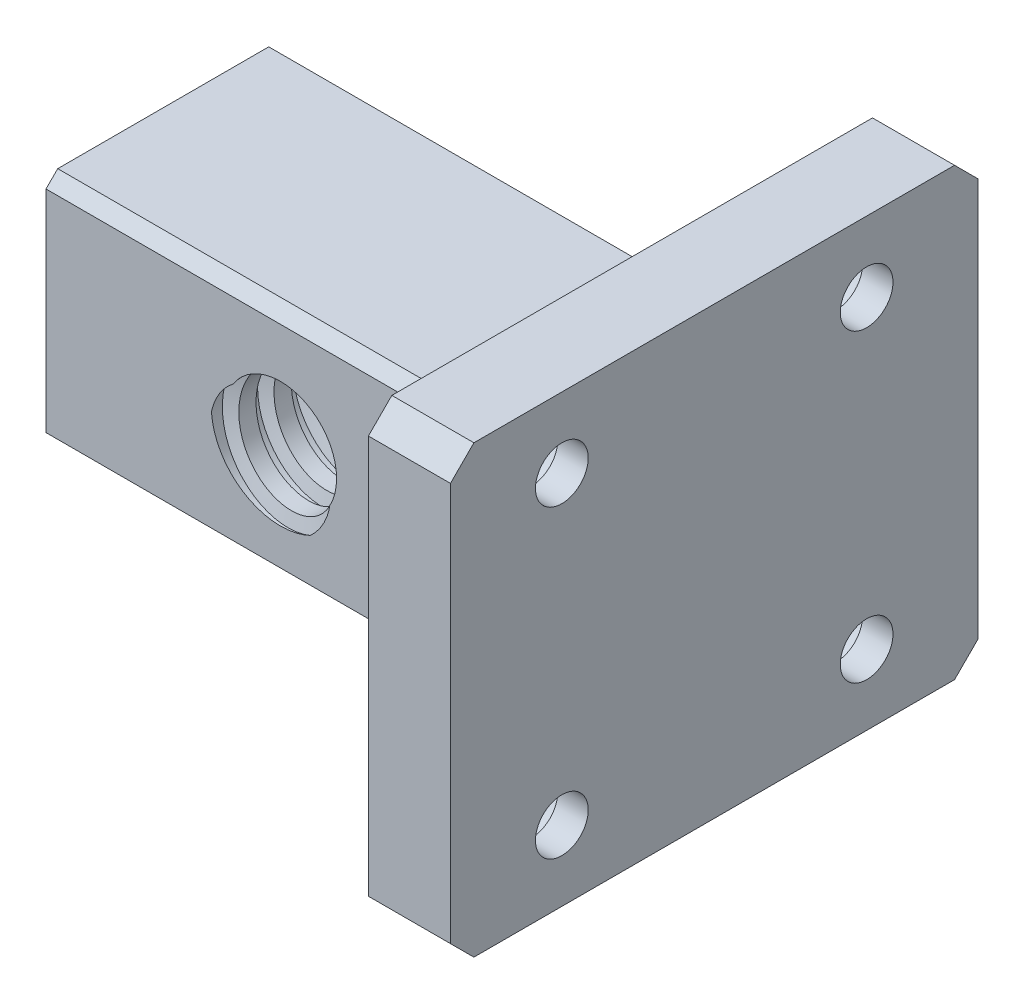
SolidWorks part; units mm, degrees
material "Brass"
ref_plane "Front Plane" through (0, 0, 0) normal (0, 0, 1) x (1, 0, 0)
ref_plane "Top Plane" through (0, 0, 0) normal (0, 1, 0) x (1, 0, 0)
ref_plane "Right Plane" through (0, 0, 0) normal (1, 0, 0) x (0, 0, -1)
sketch "Sketch1" plane through (0, 0, 0) normal (0, 0, 1) x (1, 0, 0)
  line L1 (-20, 10) -> (20, 10)
  line L2 (-20, 10) -> (-20, -10)
  line L3 (-20, -10) -> (20, -10)
  line L4 (20, 10) -> (20, -10)
  line L5 (-20, 10) -> (20, -10) construction
  line L6 (-20, -10) -> (20, 10) construction
  point P0 (0, 0)
  dimension "D1" = 40
  dimension "D2" = 20
extrude "Boss-Extrude1" add sketch "Sketch1" along normal blind 20
sketch "Sketch2" plane through (0, 0, 20) normal (0, 0, 1) x (1, 0, 0)
  circle A0 centre (0, 0) radius 4.7883
  dimension "D1" = 9.5767
fillet "Fillet1" [suppressed] radius 1
sketch "Sketch4" [suppressed] plane through (0, 10, 0) normal (0, 1, 0) x (1, 0, 0)
  line L0 (-20, -19) -> (-20, 0) construction
  line L1 (-20, 0) -> (20, 0) construction
  line L2 (20, -20) -> (-19, -20) construction
  line L3 (20, -1) -> (20, -19) construction
  point P0 (-16, -4)
  point P1 (16, -4)
  point P2 (16, -16)
  point P3 (-16, -16)
  dimension "D1" = 4
  dimension "D2" = 4
  dimension "D3" = 4
  dimension "D4" = 4
extrude "Cut-Extrude2" cut sketch "Sketch2" against normal up to next contours A0
sketch "Sketch7" plane through (0, 0, 20) normal (0, 0, 1) x (1, 0, 0)
  circle A0 centre (0, 0) radius 3.9
  dimension "D1" = 7.8
curve "Helix/Spiral1" pitch 3 height 33 radius 3.9 centre (0, 0, 20) axis (0, 0, -1) start towards (1, 0, 0)
ref_plane "Plane1" through (3.9, 0, 20) normal (0, -0.9926, -0.1215) x (-1, 0, 0)
sketch "Sketch8" plane through (3.9, 0, 20) normal (0, -0.9926, -0.1215) x (-1, 0, 0)
  line L0 (0, 0) -> (0, -2)
  line L1 (0, -2) -> (-2, -1.4641)
  line L2 (-2, -1.4641) -> (-2, -0.5359)
  line L4 (-2, -0.5359) -> (0, 0)
  point P2 (3.9, 19.8518)
  dimension "D1" = 30
  dimension "D2" = 2
  dimension "D3" = 2
sweep "Cut-Sweep1" cut profiles "Sketch8" path "Helix/Spiral1" align with end faces yes
sketch "Sketch10" plane through (20, 0, 0) normal (1, 0, 0) x (0, 0, -1)
  line L0 (0, 0) -> (-20, 0) construction
  line L1 (-32.5, 19) -> (12.5, 19)
  line L2 (-32.5, 19) -> (-32.5, -19)
  line L3 (-32.5, -19) -> (12.5, -19)
  line L4 (12.5, 19) -> (12.5, -19)
  line L5 (-20, -10) -> (-20, 10) construction
  line L6 (-20, 0) -> (-10, 10) construction
  line L7 (-20, 10) -> (0, 10) construction
  line L8 (-10, 10) -> (-10, -10) construction
  line L9 (-20, -10) -> (0, -10) construction
  dimension "D1" = 38
  dimension "D2" = 45
extrude "Extrude1" add sketch "Sketch10" along normal blind 7
chamfer "Chamfer1" distance 2 angle 45 4 edges at (23.5, -19, -12.5) (23.5, -19, 32.5) (23.5, 19, 32.5) (23.5, 19, -12.5)
hole_wizard "CBORE for M4 Hex Socket Head Cap Screw2" positions "Sketch11" profile "Sketch12" counterbore size "M4" standard "DIN" end condition through all
sketch "Sketch11" plane through (20, 0, 0) normal (-1, 0, 0) x (0, 0, 1)
  line L0 (-12.5, 0) -> (32.5, 0) construction
  line L1 (-12.5, -17) -> (-12.5, 17) construction
  line L2 (32.5, 17) -> (32.5, -17) construction
  line L3 (32.5, 0) -> (10, -19) construction
  line L4 (30.5, -19) -> (-10.5, -19) construction
  line L5 (10, -19) -> (10, 19) construction
  line L6 (-10.5, 19) -> (30.5, 19) construction
  point P0 (23, 13)
  point P2 (23, -13)
  point P4 (-3, -13)
  point P6 (-3, 13)
  dimension "D1" = 26
  dimension "D2" = 26
sketch "Sketch12" plane through (20, 13, 23) normal (0, 1, 0) x (0, 0, 1)
  line L0 (0, 0) -> (0, 7)
  line L1 (0, 7) -> (2.25, 7)
  line L3 (2.25, 7) -> (2.25, 4.4)
  line L4 (2.25, 4.4) -> (4, 4.4)
  line L5 (4, 4.4) -> (4, 0)
  line L7 (4, 0) -> (0, 0)
  line L11 (0, -6.35) -> (0, 107.95) construction
  dimension "Thru Hole Dia." = 4.5
  dimension "Thru Hole Depth" = 7
  dimension "C'Bore Dia." = 8
  dimension "C'Bore Depth" = 4.4
chamfer "Chamfer2" distance 1 angle 45 4 edges at (0, 10, 0) (0, 10, 20) (0, -10, 20) (0, -10, 0)
